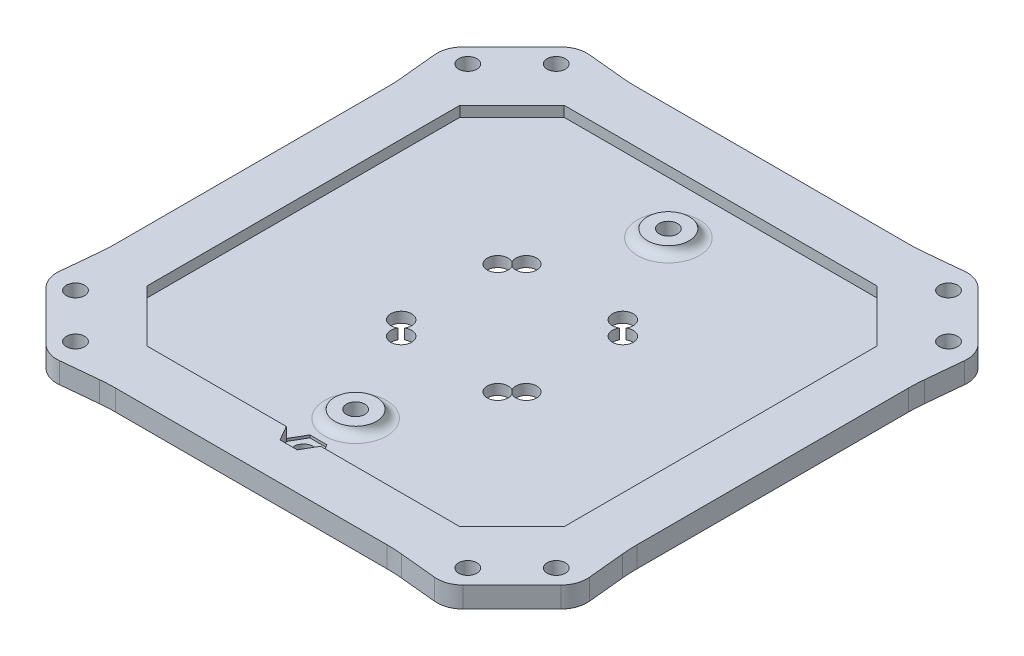
SolidWorks part; units mm, degrees
material "PP Copolymer"
ref_plane "Front Plane" through (0, 0, 0) normal (0, 0, 1) x (1, 0, 0)
ref_plane "Top Plane" through (0, 0, 0) normal (0, 1, 0) x (1, 0, 0)
ref_plane "Right Plane" through (0, 0, 0) normal (1, 0, 0) x (0, 0, -1)
sketch "Sketch1" plane through (0, 0, 0) normal (0, 1, 0) x (1, 0, 0)
  line L0 (50, 0) -> (-50, 0) construction
  line L5 (-50, -50) -> (50, -50) construction
  line L7 (-50, -50) -> (-50, 50) construction
  line L12 (-50, 50) -> (50, 50) construction
  line L25 (50, -50) -> (50, 50) construction
  line L26 (50, 50) -> (44.6967, 44.6967) construction
  line L27 (-50, 50) -> (50, -50) construction
  line L28 (0, 50) -> (0, -50) construction
  line L29 (-27.5164, 50) -> (27.5164, 50)
  line L30 (50, 27.5164) -> (50, -27.5164)
  line L31 (27.5164, -50) -> (-27.5164, -50)
  line L32 (-50, -27.5164) -> (-50, 27.5164)
  line L33 (37.6256, 46.1109) -> (46.1109, 37.6256) construction
  line L34 (38.3327, 51.0607) -> (51.0607, 38.3327)
  line L35 (27.5164, 50) -> (38.3327, 51.0607)
  line L36 (50, 27.5164) -> (51.0607, 38.3327)
  line L37 (50, -27.5164) -> (51.0607, -38.3327)
  line L38 (51.0607, -38.3327) -> (38.3327, -51.0607)
  line L39 (27.5164, -50) -> (38.3327, -51.0607)
  line L40 (-27.5164, -50) -> (-38.3327, -51.0607)
  line L41 (-38.3327, -51.0607) -> (-51.0607, -38.3327)
  line L42 (-50, -27.5164) -> (-51.0607, -38.3327)
  line L43 (-50, 27.5164) -> (-51.0607, 38.3327)
  line L44 (-51.0607, 38.3327) -> (-38.3327, 51.0607)
  line L45 (-27.5164, 50) -> (-38.3327, 51.0607)
  line L46 (41.8683, 41.8683) -> (44.6967, 44.6967) construction
  circle A8 centre (37.6256, 46.1109) radius 1.75
  circle A9 centre (46.1109, 37.6256) radius 1.75
  circle A10 centre (37.6256, -46.1109) radius 1.75
  circle A11 centre (46.1109, -37.6256) radius 1.75
  circle A12 centre (-46.1109, -37.6256) radius 1.75
  circle A13 centre (-37.6256, -46.1109) radius 1.75
  circle A14 centre (-37.6256, 46.1109) radius 1.75
  circle A15 centre (-46.1109, 37.6256) radius 1.75
  point P0 (0, 0)
  dimension "D12" = 45
  dimension "D5" = 3.5
  dimension "D1" = 100
  dimension "D2" = 12
  dimension "D3" = 4
  dimension "D4" = 18
  dimension "D7" = 5.601
  dimension "D8" = 100
  dimension "D9" = 12
  dimension "D10" = 18
  dimension "D11" = 7.5
  dimension "D13" = 75.2513
  dimension "D14" = 75.2513
  dimension "D6" = 92.2218
  dimension "D15" = 75.2513
extrude "Boss-Extrude1" add sketch "Sketch1" along normal blind 4
sketch "Sketch2" plane through (0, 4, 0) normal (0, 1, 0) x (1, 0, 0)
  line L0 (0, 0) -> (0, 40) construction
  line L2 (0, 0) -> (-40, 0) construction
  line L4 (-40, -30) -> (-40, 30)
  line L5 (-40, 30) -> (-30, 40)
  line L6 (-30, 40) -> (30, 40)
  line L7 (30, 40) -> (40, 30)
  line L8 (40, 30) -> (40, -30)
  line L9 (40, -30) -> (30, -40)
  line L10 (30, -40) -> (-30, -40)
  line L11 (-30, -40) -> (-40, -30)
  dimension "D1" = 45
  dimension "D2" = 80
  dimension "D3" = 80
  dimension "D4" = 60
extrude "Cut-Extrude1" cut sketch "Sketch2" against normal blind 2
sketch "Sketch3" [suppressed] plane through (0, 2, 0) normal (0, 1, 0) x (1, 0, 0)
  line L0 (0, 0) -> (-40, 0) construction
  line L1 (-40, 30) -> (-40, -30) construction
  line L2 (-29.0716, 16.2981) -> (-21.0716, 9.5853)
  line L3 (-20, 7.2872) -> (-20, -7.2872)
  line L4 (-21.0716, -9.5853) -> (-29.0716, -16.2981)
  line L5 (-34, 14) -> (-34, -14)
  line L10 (34, -14) -> (34, 14)
  line L11 (21.0716, 9.5853) -> (29.0716, 16.2981)
  line L12 (20, -7.2872) -> (20, 7.2872)
  line L13 (29.0716, -16.2981) -> (21.0716, -9.5853)
  line L14 (-14, -34) -> (14, -34)
  line L15 (9.5853, -21.0716) -> (16.2981, -29.0716)
  line L16 (-7.2872, -20) -> (7.2872, -20)
  line L17 (-16.2981, -29.0716) -> (-9.5853, -21.0716)
  line L18 (0, 23) -> (0, -23) construction
  line L19 (7.2872, -23) -> (-7.2872, -23) construction
  line L20 (7.2872, 23) -> (-7.2872, 23) construction
  line L21 (-16.2981, 29.0716) -> (-9.5853, 21.0716)
  line L22 (-7.2872, 20) -> (7.2872, 20)
  line L23 (9.5853, 21.0716) -> (16.2981, 29.0716)
  line L24 (-14, 34) -> (14, 34)
  line L25 (0, -23) -> (0, -34) construction
  arc A0 (-29.0716, -16.2981) -> (-34, -14) centre (-31, -14) cw
  arc A1 (-20, -7.2872) -> (-21.0716, -9.5853) centre (-23, -7.2872) cw
  arc A2 (-21.0716, 9.5853) -> (-20, 7.2872) centre (-23, 7.2872) cw
  arc A3 (-29.0716, 16.2981) -> (-34, 14) centre (-31, 14) ccw
  arc A8 (29.0716, -16.2981) -> (34, -14) centre (31, -14) ccw
  arc A9 (29.0716, 16.2981) -> (34, 14) centre (31, 14) cw
  arc A10 (20, 7.2872) -> (21.0716, 9.5853) centre (23, 7.2872) cw
  arc A11 (21.0716, -9.5853) -> (20, -7.2872) centre (23, -7.2872) cw
  arc A12 (-16.2981, -29.0716) -> (-14, -34) centre (-14, -31) ccw
  arc A13 (16.2981, -29.0716) -> (14, -34) centre (14, -31) cw
  arc A14 (7.2872, -20) -> (9.5853, -21.0716) centre (7.2872, -23) cw
  arc A15 (-9.5853, -21.0716) -> (-7.2872, -20) centre (-7.2872, -23) cw
  arc A16 (-9.5853, 21.0716) -> (-7.2872, 20) centre (-7.2872, 23) ccw
  arc A17 (7.2872, 20) -> (9.5853, 21.0716) centre (7.2872, 23) ccw
  arc A18 (16.2981, 29.0716) -> (14, 34) centre (14, 31) ccw
  arc A19 (-16.2981, 29.0716) -> (-14, 34) centre (-14, 31) cw
  point P13 (-34, -20.4335)
  point P16 (-20, -8.6861)
  point P19 (-20, 8.6861)
  point P22 (-34, 20.4335)
  point P62 (0, 0)
  point P69 (0, 0)
  dimension "D3" = 3
  dimension "D5" = 14
  dimension "D7" = 14.5744
  dimension "D8" = 50
  dimension "D4" = 46
  dimension "D9" = 62
  dimension "D10" = 62
  dimension "D11" = 50
  dimension "D2" = 20
  dimension "D6" = 100
  dimension "D12" = 20
  dimension "D13" = 28
  dimension "D14" = 28
extrude "Cut-Extrude2" [suppressed] cut sketch "Sketch3" against normal blind 1.5
sketch "Sketch4" plane through (0, 2, 0) normal (0, 1, 0) x (1, 0, 0)
  line L1 (0, 0) -> (0, 30) construction
  line L3 (0, 0) -> (0, 30) construction
  circle A0 centre (0, 30) radius 1.75
  dimension "D2" = 3.5
  dimension "D3" = 30
extrude "Cut-Extrude3" cut sketch "Sketch4" against normal through all
sketch "Sketch5" plane through (0, 2, 0) normal (0, 1, 0) x (1, 0, 0)
  circle A0 centre (0, 30) radius 4
  circle A2 centre (0, 30) radius 1.75
  circle A3 centre (0, 30) radius 1.75 construction
  dimension "D1" = 8
extrude "Boss-Extrude2" add sketch "Sketch5" along normal blind 1.5
ref_axis "Axis1" through (0, 4.2, 0) along (0, -1, 0)
mirror "Simetría1" about plane through (0, 0, 0) normal (0, 0, 1) of "Boss-Extrude2", "Cut-Extrude3"
mirror "Simetría2" [suppressed] about plane through (0, 0, 0) normal (0, 0, 1)
fillet "Redondeo1" radius 2 2 edges at (0, 2, 26) (0, 2, -34)
fillet "Redondeo2" radius 30 8 edges at (50, 2, -27.5164) (50, 2, 27.5164) (27.5164, 2, 50) (-27.5164, 2, 50) (-50, 2, 27.5164) (-50, 2, -27.5164) (-27.5164, 2, -50) (27.5164, 2, -50)
fillet "Redondeo3" radius 5 8 edges at (38.3327, 2, 51.0607) (51.0607, 2, 38.3327) (51.0607, 2, -38.3327) (38.3327, 2, -51.0607) (-38.3327, 2, -51.0607) (-51.0607, 2, -38.3327) (-51.0607, 2, 38.3327) (-38.3327, 2, 51.0607)
sketch "Croquis2" [suppressed] plane through (0, 2, 0) normal (0, 1, 0) x (1, 0, 0)
  line L1 (6, -34) -> (-6, -34)
  line L2 (6, -34) -> (6, -46)
  line L3 (6, -46) -> (-6, -46)
  line L4 (-6, -34) -> (-6, -46)
  line L5 (6, -34) -> (-6, -46) construction
  line L6 (6, -46) -> (-6, -34) construction
  point P0 (0, -40)
  dimension "D1" = 40
  dimension "D2" = 12
  dimension "D3" = 16.9706
extrude "Saliente-Extruir1" [suppressed] add sketch "Croquis2" along normal up to surface (2 mm away)
sketch "Croquis3" plane through (0, 4, 0) normal (0, 1, 0) x (1, 0, 0)
  line L0 (1.5877, -37.25) -> (3.1754, -40) construction
  line L1 (-3.1754, -40) -> (-1.5877, -42.75) construction
  line L2 (1.5877, -37.25) -> (-1.5877, -37.25) construction
  line L3 (-1.5877, -37.25) -> (-3.1754, -40) construction
  line L4 (-1.5877, -42.75) -> (1.5877, -42.75) construction
  line L5 (1.5877, -42.75) -> (3.1754, -40) construction
  line L6 (1.5877, -42.75) -> (-1.5877, -37.25) construction
  line L7 (1.5877, -37.25) -> (-1.5877, -42.75) construction
  line L8 (3.1754, -40) -> (-3.1754, -40) construction
  line L9 (1.6454, -37.15) -> (3.2909, -40)
  line L10 (1.6454, -42.85) -> (3.2909, -40)
  line L11 (-1.6454, -42.85) -> (1.6454, -42.85)
  line L12 (-3.2909, -40) -> (-1.6454, -42.85)
  line L13 (-1.6454, -37.15) -> (-3.2909, -40)
  line L14 (1.6454, -37.15) -> (-1.6454, -37.15)
  point P4 (0, -40)
  dimension "D3" = 40
  dimension "D1" = 3.1754
  dimension "D2" = 5.5
  dimension "D6" = 0.1
extrude "Cortar-Extruir2" cut sketch "Croquis3" against normal blind 2.5
sketch "Croquis1" plane through (0, 0, 0) normal (0, -1, 0) x (1, 0, 0)
  circle A0 centre (0, 40) radius 1.75
  dimension "D1" = 3.5
  dimension "D2" = 40
extrude "Cortar-Extruir1" cut sketch "Croquis1" against normal blind 5
fillet "Redondeo4" [suppressed] radius 3
fillet "Redondeo5" [suppressed] radius 5
sketch "Croquis5" plane through (0, 0, 0) normal (0, -1, 0) x (1, 0, 0)
  line L1 (12, 9.25) -> (-12, 9.25) construction
  line L2 (12, 9.25) -> (12, -9.25) construction
  line L3 (12, -9.25) -> (-12, -9.25) construction
  line L4 (-12, 9.25) -> (-12, -9.25) construction
  line L5 (12, 9.25) -> (-12, -9.25) construction
  line L6 (12, -9.25) -> (-12, 9.25) construction
  line L7 (-9.25, -12) -> (9.25, -12) construction
  line L8 (-9.25, -12) -> (-9.25, 12) construction
  line L9 (-9.25, 12) -> (9.25, 12) construction
  line L10 (9.25, -12) -> (9.25, 12) construction
  line L11 (-9.25, -12) -> (9.25, 12) construction
  line L12 (-9.25, 12) -> (9.25, -12) construction
  circle A0 centre (-12, -9.25) radius 2
  circle A1 centre (-12, 9.25) radius 2
  circle A2 centre (12, 9.25) radius 2
  circle A3 centre (12, -9.25) radius 2
  circle A4 centre (9.25, -12) radius 2
  circle A5 centre (-9.25, -12) radius 2
  circle A6 centre (9.25, 12) radius 2
  circle A7 centre (-9.25, 12) radius 2
  point P2 (0, 0)
  point P10 (0, 0)
  dimension "D1" = 18.5
  dimension "D2" = 4
  dimension "D3" = 24
extrude "Cortar-Extruir3" cut sketch "Croquis5" against normal through all both and the other way through all contours A2 | A0 | A4 | A5 | A1 | A7 | A6 | A3
sketch "Croquis6" plane through (0, 0, 0) normal (0, -1, 0) x (1, 0, 0)
  line L0 (0, 0) -> (0, -43.5) construction
  line L1 (-12.6, -43.5) -> (-7.4, -43.5)
  line L2 (-12.6, -43.5) -> (-12.6, -40.3)
  line L3 (-12.6, -40.3) -> (-7.4, -40.3)
  line L4 (-7.4, -43.5) -> (-7.4, -40.3)
  line L5 (-12.6, -43.5) -> (-7.4, -40.3) construction
  line L6 (-12.6, -40.3) -> (-7.4, -43.5) construction
  line L7 (12.6, -40.3) -> (7.4, -43.5) construction
  line L8 (12.6, -43.5) -> (7.4, -40.3) construction
  line L9 (7.4, -43.5) -> (7.4, -40.3)
  line L10 (12.6, -40.3) -> (7.4, -40.3)
  line L11 (12.6, -43.5) -> (12.6, -40.3)
  line L12 (12.6, -43.5) -> (7.4, -43.5)
  point P0 (-10, -41.9)
  point P12 (10, -41.9)
  dimension "D1" = 3.2
  dimension "D2" = 43.5
  dimension "D3" = 5.2
  dimension "D4" = 14.8
extrude "Cortar-Extruir4" cut sketch "Croquis6" against normal blind 2.5
